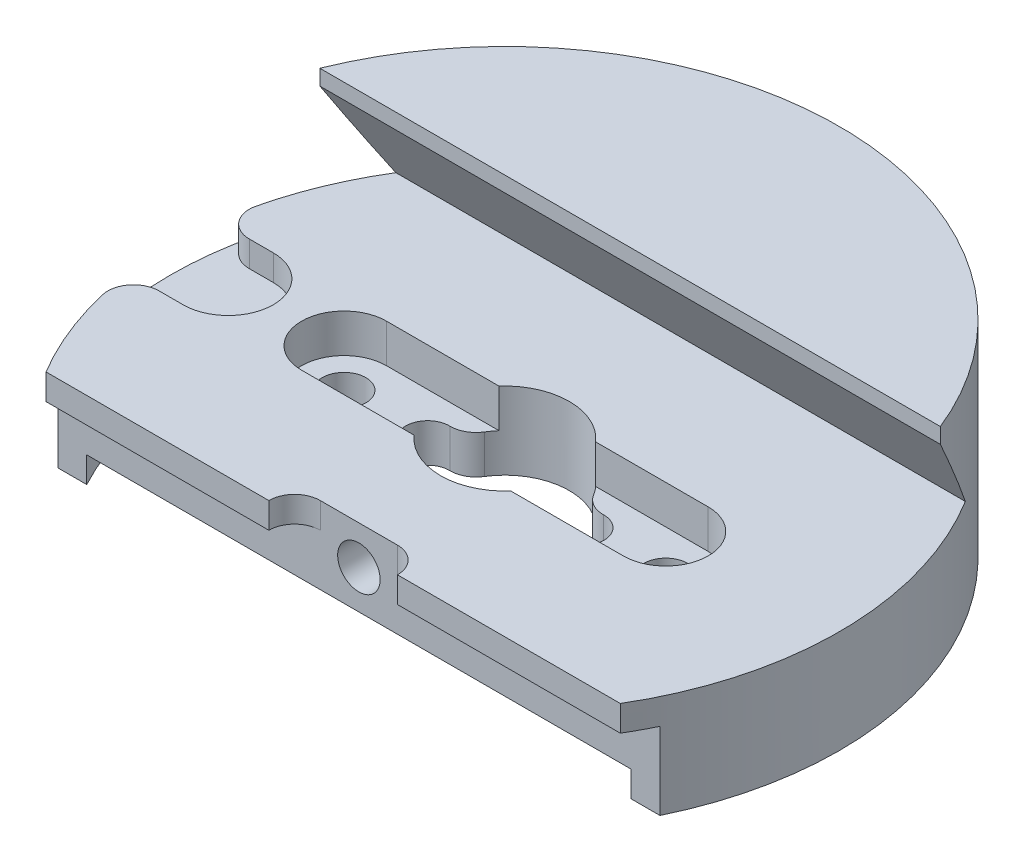
SolidWorks part; units mm, degrees
material "Сплав 2024"
ref_plane "Спереди" through (0, 0, 0) normal (0, 0, 1) x (1, 0, 0)
ref_plane "Сверху" through (0, 0, 0) normal (0, 1, 0) x (1, 0, 0)
ref_plane "Справа" through (0, 0, 0) normal (1, 0, 0) x (0, 0, -1)
sketch "Эскиз1" plane through (0, 0, 0) normal (0, 1, 0) x (1, 0, 0)
  circle A0 centre (0, 0) radius 26
  dimension "D1" = 52
extrude "Бобышка-Вытянуть1" add sketch "Эскиз1" along normal blind 14
sketch "Эскиз2" plane through (0, 0, 0) normal (1, 0, 0) x (0, 0, -1)
  line L0 (0, 14) -> (0, 0) construction
  line L1 (26, 14) -> (-26, 14) construction
  line L2 (13.6547, 6) -> (-13.6547, 6)
  line L3 (-13.6547, 6) -> (-9.7287, 12.8)
  line L4 (-9.7287, 12.8) -> (-9.7287, 14)
  line L5 (-9.7287, 14) -> (9.7287, 14)
  line L6 (0, 14) -> (0, 6) construction
  line L7 (13.6547, 6) -> (9.7287, 12.8)
  line L8 (9.7287, 12.8) -> (9.7287, 14)
  line L9 (-12.5, 8) -> (-12.5, 6) construction
  dimension "D1" = 8
  dimension "D2" = 1.2
  dimension "D3" = 60
  dimension "D4" = 13.6547
  dimension "D5" = 9.7287
  dimension "D6" = 2
  dimension "D7" = 12.5
extrude "Вырез-Вытянуть1" cut sketch "Эскиз2" against normal mid plane 60
sketch "Примерка" plane through (0, 0, 0) normal (1, 0, 0) x (0, 0, -1)
  line L0 (13.6547, 6) -> (-13.6547, 6) construction
  line L1 (-12.5, 14) -> (12.5, 14)
  line L2 (-12.5, 14) -> (-12.5, 6)
  line L3 (-12.5, 6) -> (12.5, 6)
  line L4 (12.5, 14) -> (12.5, 6)
  point P6 (0, 6)
  dimension "D1" = 8
  dimension "D2" = 25
sketch "Эскиз6" plane through (0, 6, 0) normal (0, 1, 0) x (1, 0, 0)
  line L1 (18.4208, 0) -> (-15.4735, 0) construction
  circle A0 centre (0, 0) radius 6 construction
  circle A1 centre (0, 0) radius 12.5 construction
  dimension "D1" = 12
  dimension "D2" = 25
hole_wizard "Цековка для винта с внутренним шестигранником M32" positions "Эскиз14" profile "Эскиз13" counterbore size "M3" standard "Ansi Metric" end condition up to next
sketch "Эскиз14" plane through (0, 6, 0) normal (0, 1, 0) x (1, 0, 0)
  line L0 (18.4208, 0) -> (-15.4735, 0) construction
  circle A0 centre (0, 0) radius 12.5 construction
  circle A1 centre (0, 0) radius 6 construction
  point P0 (-12.5, 0)
  point P6 (12.5, 0)
  point P20 (-6, 0)
  point P24 (6, 0)
sketch "Эскиз13" plane through (-12.5, 6, 0) normal (1, 0, 0) x (0, 0, 1)
  line L0 (0, 0) -> (0, 6)
  line L1 (0, 6) -> (1.7, 6)
  line L3 (1.7, 6) -> (1.7, 3)
  line L4 (1.7, 3) -> (3.3, 3)
  line L5 (3.3, 3) -> (3.3, 0)
  line L7 (3.3, 0) -> (0, 0)
  line L11 (0, -6.35) -> (0, 107.95) construction
  dimension "Диаметр сквозного отверстия" = 3.4
  dimension "Глубина сквозного отверстия" = 6
  dimension "Диаметр цековки" = 6.6
  dimension "Глубина цековки" = 3
sketch "Эскиз12" plane through (0, 0, 0) normal (0, -1, 0) x (1, 0, 0)
  circle A0 centre (0, 0) radius 26 construction
  circle A1 centre (0, 0) radius 26
  circle A3 centre (0, 0) radius 24
  dimension "D1" = 2
extrude "Бобышка-Вытянуть2" add sketch "Эскиз12" along normal blind 2
sketch "Эскиз17" plane through (0, 14, 0) normal (0, 1, 0) x (1, 0, 0)
  line L0 (-24.1112, -9.7287) -> (24.1112, -9.7287) construction
  line L1 (-24.1112, -9.7287) -> (24.1112, -9.7287)
  arc A0 (-24.1112, -9.7287) -> (24.1112, -9.7287) centre (0, 0) ccw construction
  arc A1 (-24.1112, -9.7287) -> (24.1112, -9.7287) centre (0, 0) ccw
extrude "Вырез-Вытянуть4" cut sketch "Эскиз17" against normal up to surface (8 mm away) up to face at (9.25, 6, 0)
sketch "Эскиз18" plane through (0, 0, 0) normal (0, -1, 0) x (1, 0, 0)
  circle A0 centre (0, 0) radius 5
  dimension "D1" = 10
extrude "Вырез-Вытянуть5" cut sketch "Эскиз18" against normal up to next
sketch "Эскиз19" plane through (0, 6, 0) normal (0, 1, 0) x (1, 0, 0)
  line L0 (-22.3137, -13.3453) -> (22.3137, -13.3453)
  line L1 (-22.1258, 13.6547) -> (22.1258, 13.6547) construction
  arc A0 (-22.1258, 13.6547) -> (22.1258, 13.6547) centre (0, 0) ccw construction
  arc A1 (-22.3137, -13.3453) -> (22.3137, -13.3453) centre (0, 0) ccw
  dimension "D1" = 27
extrude "Вырез-Вытянуть6" cut sketch "Эскиз19" against normal blind 10
sketch "Эскиз21" plane through (0, 0, 13.3453) normal (0, 0, 1) x (1, 0, 0)
  line L0 (0, 0) -> (0, 6) construction
  line L1 (19.9475, 0) -> (-19.9475, 0) construction
  line L2 (22.3137, 6) -> (-22.3137, 6) construction
  point P6 (0, 3)
  dimension "D1" = 3
hole_wizard "Отверстие обработанное метчиком M4x0.71" positions "Эскиз23" profile "Эскиз22" tap size "M4x0.7" standard "Ansi Metric"
sketch "Эскиз23" plane through (0, 0, 13.3453) normal (0, 0, 1) x (1, 0, 0)
  point P4 (0, 3)
sketch "Эскиз22" plane through (0, 3, 13.3453) normal (1, 0, 0) x (0, -1, 0)
  line L0 (0, 0) -> (0, 12.4914)
  line L1 (0, 12.4914) -> (1.65, 11.5)
  line L2 (1.65, 11.5) -> (1.65, 0)
  line L5 (1.65, 0) -> (0, 0)
  line L10 (0, 12.4914) -> (-1.65, 11.5) construction
  line L11 (0, -6.35) -> (0, 107.95) construction
  dimension "Диаметр сверла" = 3.3
  dimension "Глубина сверла" = 11.5
  dimension "Угол заточки сверла" = 118
cosmetic thread "Отверстие резьбы1" parameters "D1"=8, "D2"=4
sketch "Эскиз20" plane through (0, 0, 13.3453) normal (0, 0, 1) x (1, 0, 0)
  line L0 (0, 3.1198) -> (0, -5.6063) construction
  line L1 (22.3137, 6) -> (-22.3137, 6) construction
  line L2 (-25.198, 4) -> (-5, 4)
  line L3 (-25.198, 4) -> (-25.198, -2)
  line L4 (-25.198, -2) -> (25.198, -2)
  line L5 (25.198, 4) -> (25.198, -2)
  line L6 (-25.198, 4) -> (25.198, -2) construction
  line L7 (-25.198, -2) -> (25.198, 4) construction
  line L8 (-22.3137, -2) -> (-19.9475, -2) construction
  line L9 (-22.1258, 6) -> (22.1258, 6) construction
  line L10 (5, 4) -> (5, 6)
  line L11 (5, 4) -> (25.198, 4)
  line L12 (-5, 6) -> (5, 6)
  line L14 (-5, -4) -> (5, 6) construction
  line L15 (-5, 6) -> (5, -4) construction
  line L16 (-5, 4) -> (-5, 6)
  point P3 (0, 1)
  point P12 (0, 1)
  dimension "D1" = 2
  dimension "D2" = 10
extrude "Вырез-Вытянуть7" cut sketch "Эскиз20" against normal blind 2
sketch "Эскиз24" plane through (0, 6, 0) normal (0, 1, 0) x (1, 0, 0)
  line L0 (-30.5, 0) -> (-21.5, 0) construction
  line L1 (-30.5, 3.5) -> (-21.5, 3.5)
  line L2 (-30.5, -3.5) -> (-21.5, -3.5)
  line L4 (0, 0) -> (-6.6582, 0) construction
  arc A0 (-22.1258, 13.6547) -> (-22.3137, -13.3453) centre (0, 0) ccw construction
  arc A1 (-30.5, 3.5) -> (-30.5, -3.5) centre (-30.5, 0) ccw
  arc A2 (-21.5, -3.5) -> (-21.5, 3.5) centre (-21.5, 0) ccw
  point P5 (-26, 0)
  dimension "D1" = 9
  dimension "D2" = 7
extrude "Вырез-Вытянуть8" cut sketch "Эскиз24" against normal blind 2
fillet "Скругление3" radius 2 2 edges at (-25.7633, 5, 3.5) (-25.7633, 5, -3.5)
sketch "Эскиз25" plane through (0, 6, 0) normal (0, 1, 0) x (1, 0, 0)
  line L0 (-12.5, 0) -> (12.5, 0) construction
  line L1 (-12.5, 3.3) -> (12.5, 3.3)
  line L2 (-12.5, -3.3) -> (12.5, -3.3)
  arc A0 (-12.5, 3.3) -> (-12.5, -3.3) centre (-12.5, 0) ccw
  arc A1 (12.5, -3.3) -> (12.5, 3.3) centre (12.5, 0) ccw
  arc A2 (9.25, -0.5723) -> (9.25, 0.5723) centre (12.5, 0) ccw construction
  point P2 (0, 0)
extrude "Вырез-Вытянуть9" cut sketch "Эскиз25" against normal up to surface (3 mm away) up to face at (-7.8743, 3, 0)
fillet "Скругление5" radius 2 4 edges at (4.8425, 1.5, -1.2451) (4.8425, 1.5, 1.2451) (-4.8425, 1.5, 1.2451) (-4.8425, 1.5, -1.2451)
sketch "Эскиз28" plane through (0, 0, 0) normal (0, -1, 0) x (1, 0, 0)
  line L0 (-23.1584, -6.3) -> (23.1584, -6.3)
  line L1 (-3.7563, -3.3) -> (-12.5, -3.3) construction
  arc A0 (-23.1584, -6.3) -> (23.1584, -6.3) centre (0, 0) ccw
  arc A1 (-21.1491, 11.3453) -> (21.1491, 11.3453) centre (0, 0) ccw construction
  dimension "D1" = 3
extrude "Вырез-Вытянуть10" cut sketch "Эскиз28" against normal blind 4
sketch "Эскиз5" plane through (0, 4, 0) normal (0, -1, 0) x (1, 0, 0)
  line L2 (-22.1258, -15.6547) -> (22.1258, -15.6547)
  line L3 (-18.0594, -15.6547) -> (18.0594, -15.6547)
  arc A3 (-18.0594, -15.6547) -> (18.0594, -15.6547) centre (0, 0) ccw
  point P4 (0, 0)
  dimension "D1" = 23.9
  dimension "D2" = 2
extrude "Вырез-Вытянуть11" cut sketch "Эскиз5" against normal offset from surface (8 mm away) 2 up to face at (0, 14, -17.8644)
fillet "Скругление8" radius 2 6 edges at (-5, 5, 11.3453) (5, 5, 11.3453) (23.1584, 2, -6.3) (18.0594, 8, -15.6547) (-23.1584, 2, -6.3) (-18.0594, 8, -15.6547)
